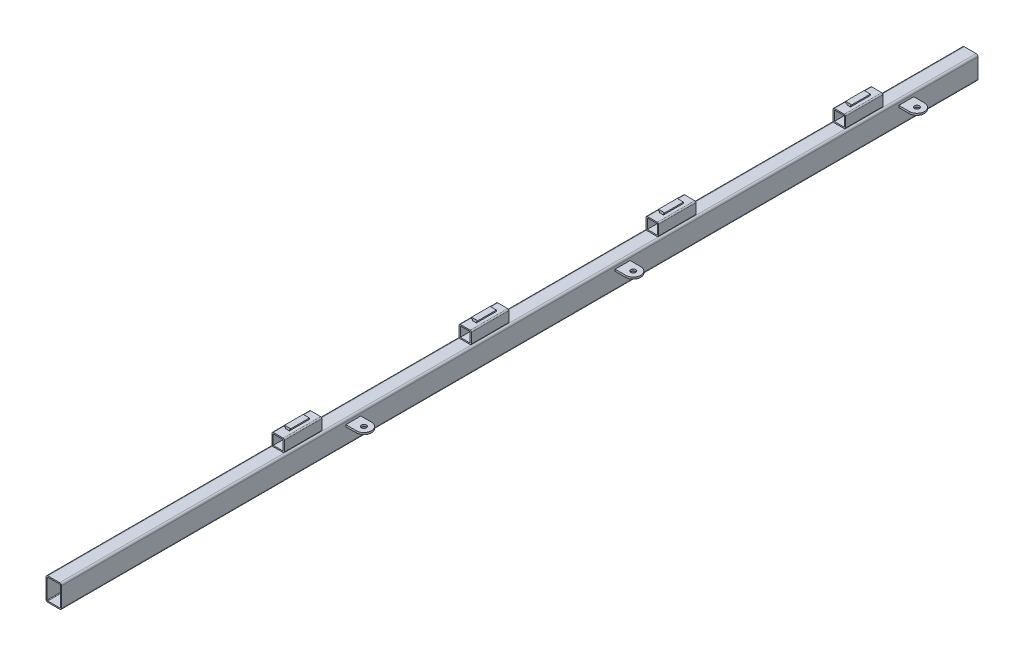
SolidWorks part; units mm, degrees
material "Alloy Steel"
ref_plane "Front" through (0, 0, 0) normal (0, 0, 1) x (1, 0, 0)
ref_plane "Top" through (0, 0, 0) normal (0, 1, 0) x (1, 0, 0)
ref_plane "Right" through (0, 0, 0) normal (1, 0, 0) x (0, 0, -1)
sketch "Sketch1" plane through (0, 0, 0) normal (0, 0, 1) x (1, 0, 0)
  line L0 (0, 40.8909) -> (0, -24.1212) construction
  line L1 (-9.5, 37) -> (9.5, 37)
  line L2 (-12.5, 34) -> (-12.5, 3)
  line L3 (-9.5, 0) -> (9.5, 0)
  line L4 (12.5, 34) -> (12.5, 3)
  arc A0 (-12.5, 3) -> (-9.5, 0) centre (-9.5, 3) ccw
  arc A1 (9.5, 0) -> (12.5, 3) centre (9.5, 3) ccw
  arc A2 (9.5, 37) -> (12.5, 34) centre (9.5, 34) cw
  arc A3 (-9.5, 37) -> (-12.5, 34) centre (-9.5, 34) ccw
  point P9 (-12.5, 0)
  point P12 (12.5, 0)
  point P15 (12.5, 37)
  dimension "D3" = 3
  dimension "D1" = 37
  dimension "D2" = 25
extrude "Extrude-Thin1" add sketch "Sketch1" along normal blind 1470 thin contours L1 A2 L4 A1 L3 A0 L2 A3 thin type one direction reverse wall 2
ref_plane "Plane1" through (0, 27, 0) normal (0, 1, 0) x (1, 0, 0)
sketch "Sketch2" plane through (0, 27, 0) normal (0, 1, 0) x (1, 0, 0)
  line L0 (29.5, -103) -> (12.5, -103)
  line L1 (12.5, -1470) -> (12.5, 0) construction
  line L2 (12.5, -103) -> (12.5, -127)
  line L3 (12.5, -127) -> (29.5, -127)
  line L4 (-9.5, 0) -> (9.5, 0) construction
  line L5 (29.5, -558) -> (12.5, -558)
  line L6 (12.5, -558) -> (12.5, -582)
  line L7 (12.5, -582) -> (29.5, -582)
  line L8 (29.5, -990) -> (12.5, -990)
  line L9 (12.5, -990) -> (12.5, -1014)
  line L10 (12.5, -1014) -> (29.5, -1014)
  arc A0 (29.5, -103) -> (29.5, -127) centre (29.5, -115) cw
  circle A1 centre (29.5, -115) radius 4
  arc A2 (29.5, -558) -> (29.5, -582) centre (29.5, -570) cw
  circle A3 centre (29.5, -570) radius 4
  arc A4 (29.5, -990) -> (29.5, -1014) centre (29.5, -1002) cw
  circle A5 centre (29.5, -1002) radius 4
  dimension "D1" = 8
  dimension "D2" = 12
  dimension "D5" = 8
  dimension "D6" = 12
  dimension "D9" = 8
  dimension "D10" = 12
  dimension "D3" = 17
  dimension "D4" = 115
  dimension "D8" = 570
  dimension "D12" = 1002
extrude "Boss-Extrude1" add sketch "Sketch2" along normal blind 3
ref_plane "Plane2" through (0, 0, 150) normal (0, 0, -1) x (-1, 0, 0)
sketch "Sketch3" plane through (0, 0, 150) normal (0, 0, -1) x (-1, 0, 0)
  line L0 (0, 62.5541) -> (0, 30.9171) construction
  line L1 (-8, 57) -> (8, 57)
  line L2 (-10, 55) -> (-10, 39)
  line L3 (-8, 37) -> (8, 37)
  line L4 (10, 55) -> (10, 39)
  line L5 (-10.5, 34) -> (-10.5, 3) construction
  line L6 (10.5, 34) -> (10.5, 3) construction
  line L7 (9.5, 37) -> (-9.5, 37) construction
  arc A0 (8, 37) -> (10, 39) centre (8, 39) ccw
  arc A1 (-10, 39) -> (-8, 37) centre (-8, 39) ccw
  arc A2 (-8, 57) -> (-10, 55) centre (-8, 55) ccw
  arc A3 (8, 57) -> (10, 55) centre (8, 55) cw
  point P14 (10, 37)
  point P21 (10, 57)
  dimension "D2" = 2
  dimension "D1" = 20
extrude "Extrude-Thin2" add sketch "Sketch3" against normal blind 60 thin contours L1 A3 L4 A0 L3 A1 L2 A2 thin type one direction reverse wall 2
ref_plane "Plane3" through (0, 0, 180) normal (0, 0, 1) x (1, 0, 0)
sketch "Sketch4" plane through (0, 0, 180) normal (0, 0, 1) x (1, 0, 0)
  line L0 (-3, 57) -> (-3, 59)
  line L2 (-3, 59) -> (-5, 59)
  line L3 (-5, 59) -> (-5, 61)
  line L4 (-5, 61) -> (5, 61)
  line L5 (5, 61) -> (5, 59)
  line L6 (5, 59) -> (3, 59)
  line L7 (3, 59) -> (3, 57)
  line L8 (3, 57) -> (-3, 57)
  line L9 (0, 63.1918) -> (0, 54.2911) construction
  line L10 (8, 57) -> (-8, 57) construction
  dimension "D1" = 2
  dimension "D2" = 10
  dimension "D3" = 6
  dimension "D4" = 2
extrude "Boss-Extrude2" add sketch "Sketch4" along normal mid plane 30
pattern_linear "LPattern1" count 4 spacing 300 along (0, 0, 1) of "Extrude-Thin2", "Boss-Extrude2"
